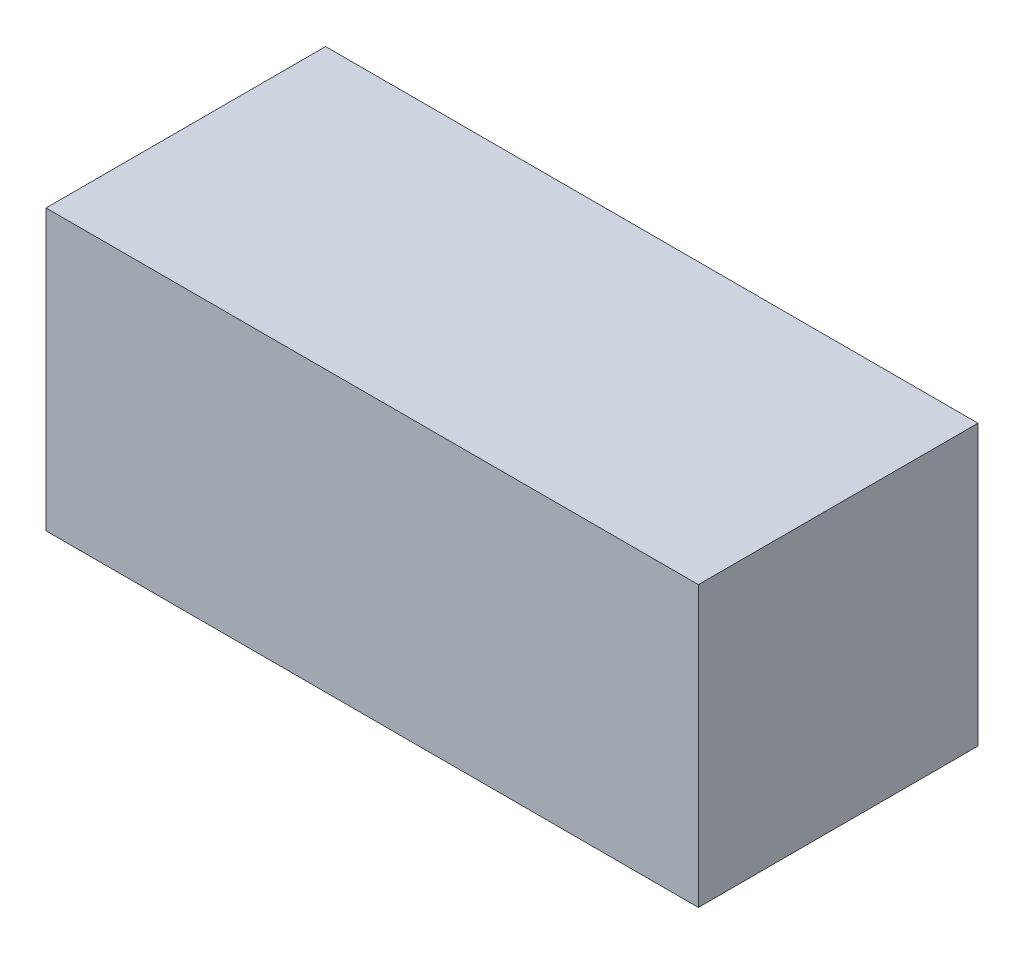
SolidWorks part; units mm, degrees
ref_plane "Front Plane" through (0, 0, 0) normal (0, 0, 1) x (1, 0, 0)
ref_plane "Top Plane" through (0, 0, 0) normal (0, 1, 0) x (1, 0, 0)
ref_plane "Right Plane" through (0, 0, 0) normal (1, 0, 0) x (0, 0, -1)
sketch "Sketch1" plane through (0, 0, 0) normal (0, 1, 0) x (1, 0, 0)
  line L1 (-35, -15) -> (35, -15)
  line L2 (-35, -15) -> (-35, 15)
  line L3 (-35, 15) -> (35, 15)
  line L4 (35, -15) -> (35, 15)
  line L5 (-35, -15) -> (35, 15) construction
  line L6 (-35, 15) -> (35, -15) construction
  point P0 (0, 0)
  dimension "D1" = 70
  dimension "D2" = 30
extrude "Boss-Extrude1" add sketch "Sketch1" along normal blind 30
equation "\"TrackerMass\"= 100'judges tracker mass"
